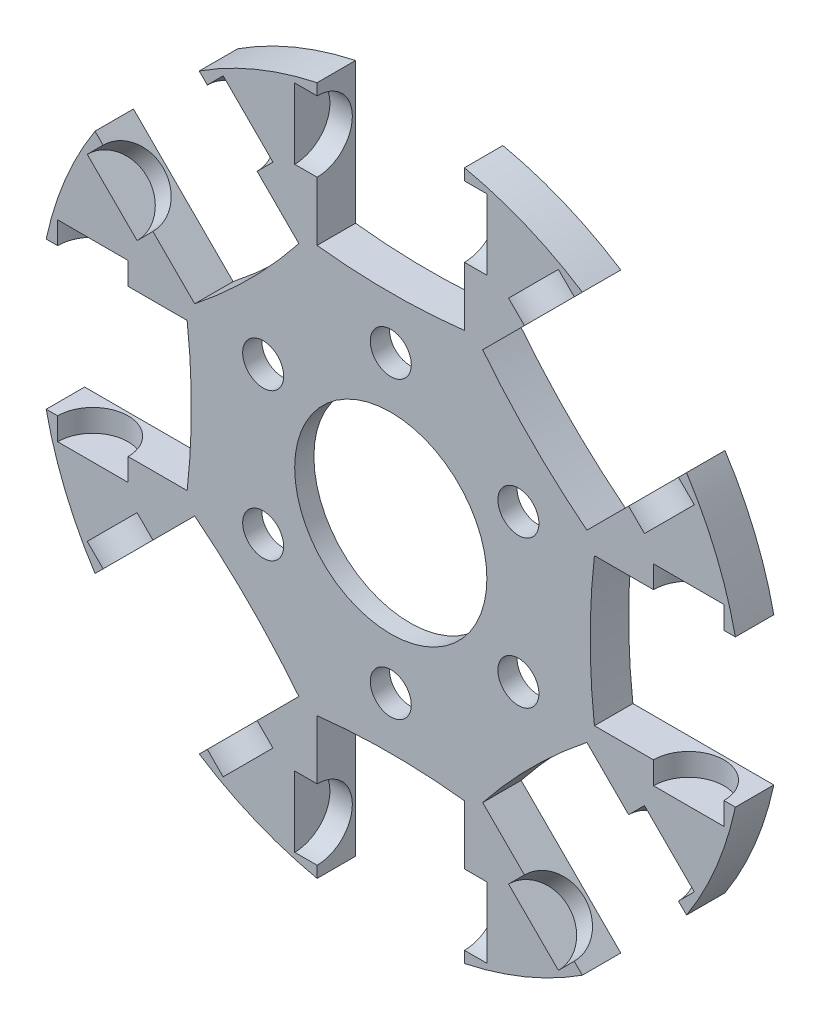
SolidWorks part; units mm, degrees
ref_plane "Front Plane" through (0, 0, 0) normal (0, 0, 1) x (1, 0, 0)
ref_plane "Top Plane" through (0, 0, 0) normal (0, 1, 0) x (1, 0, 0)
ref_plane "Right Plane" through (0, 0, 0) normal (1, 0, 0) x (0, 0, -1)
sketch "Sketch2" plane through (0, 0, 0) normal (0, 0, 1) x (1, 0, 0)
  line L0 (0, -2.3056) -> (0, 37.2834) construction
  line L1 (-5.75, 28.5556) -> (5.75, 28.5556) construction
  line L2 (-5.75, 26.8921) -> (-5.75, 15.8921)
  line L3 (5.75, 26.8921) -> (5.75, 15.8921)
  line L4 (14.9498, 23.0815) -> (7.1716, 15.3033)
  line L5 (23.0815, 14.9498) -> (15.3033, 7.1716)
  line L6 (26.8921, 5.75) -> (15.8921, 5.75)
  line L7 (26.8921, -5.75) -> (15.8921, -5.75)
  line L8 (23.0815, -14.9498) -> (15.3033, -7.1716)
  line L9 (14.9498, -23.0815) -> (7.1716, -15.3033)
  line L10 (5.75, -26.8921) -> (5.75, -15.8921)
  line L11 (-5.75, -26.8921) -> (-5.75, -15.8921)
  line L12 (-14.9498, -23.0815) -> (-7.1716, -15.3033)
  line L13 (-23.0815, -14.9498) -> (-15.3033, -7.1716)
  line L14 (-26.8921, -5.75) -> (-15.8921, -5.75)
  line L15 (-26.8921, 5.75) -> (-15.8921, 5.75)
  line L16 (-23.0815, 14.9498) -> (-15.3033, 7.1716)
  line L17 (-14.9498, 23.0815) -> (-7.1716, 15.3033)
  circle A0 centre (0, 0) radius 27.5
  circle A1 centre (0, 0) radius 11.5 construction
  circle A2 centre (0, 0) radius 14 construction
  circle A3 centre (-9.9593, 5.75) radius 1.6
  circle A4 centre (0, 11.5) radius 1.6
  circle A5 centre (9.9593, 5.75) radius 1.6
  circle A6 centre (9.9593, -5.75) radius 1.6
  circle A7 centre (0, -11.5) radius 1.6
  circle A8 centre (-9.9593, -5.75) radius 1.6
  arc A9 (-5.75, 15.8921) -> (5.75, 15.8921) centre (0, 65.5604) ccw
  arc A10 (7.1716, 15.3033) -> (15.3033, 7.1716) centre (46.3582, 46.3582) ccw
  arc A11 (15.8921, 5.75) -> (15.8921, -5.75) centre (65.5604, 0) ccw
  arc A12 (15.3033, -7.1716) -> (7.1716, -15.3033) centre (46.3582, -46.3582) ccw
  arc A13 (5.75, -15.8921) -> (-5.75, -15.8921) centre (0, -65.5604) ccw
  arc A14 (-7.1716, -15.3033) -> (-15.3033, -7.1716) centre (-46.3582, -46.3582) ccw
  arc A15 (-15.8921, -5.75) -> (-15.8921, 5.75) centre (-65.5604, 0) ccw
  arc A16 (-15.3033, 7.1716) -> (-7.1716, 15.3033) centre (-46.3582, 46.3582) ccw
  circle A19 centre (0, 0) radius 7.5
  circle A20 centre (0, 0) radius 14
  point P9 (0, 28.5556)
  point P25 (0, 0)
  point P67 (1.5089, -0.625)
  point P69 (0, 0)
  point P75 (0, 0)
  point P79 (0, 0)
  point P80 (0, 0)
  point P81 (0, 0)
  point P83 (-22.6761, 7.3679)
  dimension "D1" = 55
  dimension "D2" = 11.5
  dimension "37" = 23
  dimension "D3" = 8
  dimension "35" = 28
  dimension "D4" = 3.2
  dimension "D8" = 15
  dimension "D7" = 50
  dimension "D6" = 11
  dimension "D5" = 6
extrude "Boss-Extrude2" add sketch "Sketch2" along normal blind 3 contours A0 L3 A9 L2 A20 | A20 A3 A4 A5 A6 A7 A8 A19 region at (-6.5106, 21.3921, 0) region at (-13.604, 0, 0)
extrude "Boss-Extrude3" add sketch "Sketch2<4>" along normal blind 3 contours A20 A8 A1 A3 A4 A5 A6 A7 region at (-13.604, 0, 0)
sketch "Sketch2<4>" plane through (0, 0, 0) normal (0, 0, 1) x (1, 0, 0) same geometry as "Sketch2"
sketch "Sketch3" plane through (0, 0, 3) normal (0, 0, 1) x (1, 0, 0)
  line L0 (0, 28.1882) -> (0, 8.7236) construction
  line L1 (-4.625, 27.1083) -> (4.625, 27.1083) construction
  line L3 (-6.683, 23) -> (6.8867, 23) construction
  line L4 (-7.5, 26) -> (7.5, 26)
  line L5 (7.5, 26) -> (7.5, 23.25)
  line L6 (-7.5, 26) -> (-7.5, 23.25)
  line L7 (7.5, 23.25) -> (-7.5, 23.25)
  point P15 (0, 26)
  dimension "D1" = 23
  dimension "D2" = 15
  dimension "D3" = 3
  dimension "D4" = 2.75
revolve "Cut-Revolve1" cut sketch "Sketch3" angle 360 about L7
sketch "Sketch5" plane through (0, 0, 0) normal (0, 0, -1) x (-1, 0, 0)
  circle A0 centre (0, 0) radius 15.5
  dimension "D1" = 31
extrude "Cut-Extrude2" cut sketch "Sketch5" against normal blind 1.5
pattern_circular "CirPattern2" count 8 over 360 about axis through (0, 0, 3) along (0, 0, 1) of "Cut-Revolve1"
